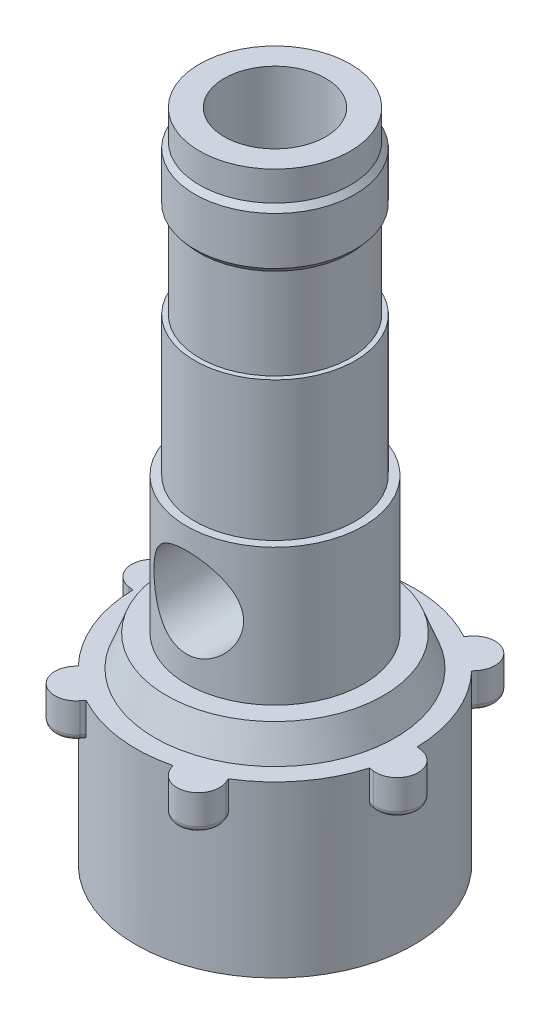
SolidWorks part; units mm, degrees
ref_plane "Front Plane" through (0, 0, 0) normal (0, 0, 1) x (1, 0, 0)
ref_plane "Top Plane" through (0, 0, 0) normal (0, 1, 0) x (1, 0, 0)
ref_plane "Right Plane" through (0, 0, 0) normal (1, 0, 0) x (0, 0, -1)
sketch "Sketch1" plane through (0, 0, 0) normal (1, 0, 0) x (0, 0, -1)
  line L0 (0, 0) -> (0, 27.8) construction
  line L1 (0, 8) -> (3, 8)
  line L2 (3, 8) -> (3, 6)
  line L3 (3, 6) -> (5, 6)
  line L4 (5, 6) -> (5, 3)
  line L5 (5, 3) -> (5.3, 0)
  line L6 (5.3, 0) -> (5.9, 0)
  line L7 (5.9, 0) -> (5.9, 7.2)
  line L8 (5.9, 7.2) -> (5.1, 7.2)
  line L9 (5.1, 7.2) -> (4.6, 8.5)
  line L10 (4.6, 8.5) -> (3.75, 8.5)
  line L11 (3.4, 14.3) -> (3.4, 20.2)
  line L12 (3.4, 20.2) -> (3.2, 20.2)
  line L13 (3.2, 20.2) -> (3.2, 24.05)
  line L14 (3.2, 24.05) -> (3.4, 24.2884)
  line L15 (3.4, 24.2884) -> (3.4, 26.3116)
  line L16 (3.4, 26.3116) -> (3.2, 26.55)
  line L17 (3.2, 26.55) -> (3.2, 27.8)
  line L18 (3.2, 27.8) -> (2.15, 27.8)
  line L19 (2.15, 27.8) -> (2.15, 18.4)
  line L20 (2.15, 18.4) -> (1.9, 18.4)
  line L21 (1.9, 18.4) -> (1.9, 11.4)
  line L22 (1.9, 11.4) -> (0, 11.4)
  line L23 (0, 11.4) -> (0, 8)
  line L24 (3.75, 8.5) -> (3.75, 14.3)
  line L25 (3.75, 14.3) -> (3.4, 14.3)
  line L26 (3.75, 11.4) -> (1.9, 11.4) construction
  point P14 (3.75, 11.4)
  dimension "D1" = 27.8
  dimension "D2" = 11.8
  dimension "D3" = 10
  dimension "D4" = 6
  dimension "D5" = 0.6
  dimension "D6" = 3
  dimension "D7" = 8
  dimension "D8" = 6
  dimension "D9" = 10.2
  dimension "D10" = 6.8
  dimension "D11" = 6.4
  dimension "D12" = 9.2
  dimension "D13" = 1.3
  dimension "D14" = 7.2
  dimension "D15" = 7.5
  dimension "D16" = 13.5
  dimension "D17" = 7.6
  dimension "D18" = 1.25
  dimension "D19" = 2.5
  dimension "D20" = 4.3
  dimension "D21" = 9.4
  dimension "D22" = 3.8
  dimension "D23" = 40
  dimension "D24" = 40
revolve "Revolve1" add sketch "Sketch1" angle 360 about L0
sketch "Sketch2" plane through (0, 0, 0) normal (0, 0, 1) x (1, 0, 0)
  line L0 (0, 11.5) -> (0, 27.8) construction
  circle A0 centre (0, 11.5) radius 1.9
  dimension "D2" = 3.8
  dimension "D1" = 16.3
extrude "Cut-Extrude1" cut sketch "Sketch2" against normal through all both and the other way through all
sketch "Sketch6" plane through (0, 7.2, 0) normal (0, 1, 0) x (1, 0, 0)
  line L0 (0, 0) -> (0, 8.8083) construction
  line L1 (0, 0) -> (-2.646, 6.3879) construction
  line L2 (-3.4775, 6.0435) -> (-3.0301, 4.9635)
  line L3 (-3.4775, 6.0435) -> (-1.8145, 6.7324)
  line L4 (-3.0301, 4.9635) -> (-1.3671, 5.6523)
  line L5 (-1.8145, 6.7324) -> (-1.3671, 5.6523)
  line L6 (-3.4775, 6.0435) -> (-1.3671, 5.6523) construction
  line L7 (-3.0301, 4.9635) -> (-1.8145, 6.7324) construction
  point P2 (-2.646, 6.3879)
  point P4 (-2.4223, 5.8479)
  point P9 (0, 0)
  point P10 (0, 0)
  point P11 (0, 0)
  dimension "D1" = 1.169
  dimension "D2" = 1.8
extrude "Boss-Extrude3" add sketch "Sketch6" against normal blind 1.5
fillet "Fillet1" 2 edges at (-1.8145, 6.45, -6.7324) (-3.4775, 6.45, -6.0435) type full round first side face at (-1.6072, 6.45, -6.2319) second side face at (-3.2702, 6.45, -5.5431) middle face at (-2.646, 6.45, -6.3879)
fillet "Fillet2" radius 0.25 3 edges at (-3.098, 5.7, -5.1274) (-1.435, 5.7, -5.8162) (-2.646, 5.7, -6.3879)
pattern_circular "CirPattern5" count 6 over 360 about axis through (0, 0, 0) along (0, -1, 0) of "Boss-Extrude3", "Fillet1" reverse direction yes
fillet "Fillet3" radius 0.25 15 edges at (2.8914, 5.7, -5.2466) (4.3195, 5.7, -4.1508) (5.9894, 5.7, -0.1192) (5.7545, 5.7, 1.6654) (3.098, 5.7, 5.1274) (1.435, 5.7, 5.8162) (-2.8914, 5.7, 5.2466) (-4.3195, 5.7, 4.1508) (-5.9894, 5.7, 0.1192) (-5.7545, 5.7, -1.6654) (4.2091, 5.7, -5.4854) (6.8551, 5.7, 0.9025) (2.646, 5.7, 6.3879) (-4.2091, 5.7, 5.4854) (-6.8551, 5.7, -0.9025)
